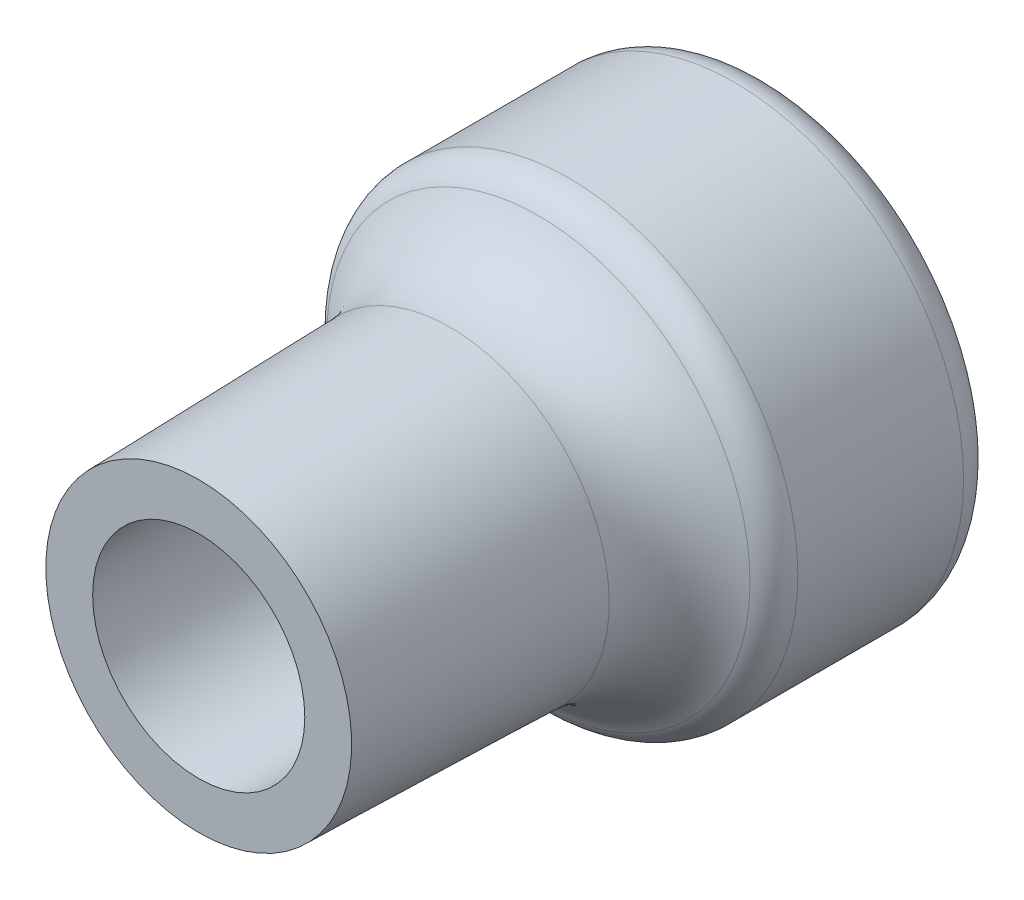
SolidWorks part; units mm, degrees
ref_plane "Front" through (0, 0, 0) normal (0, 0, 1) x (1, 0, 0)
ref_plane "Top" through (0, 0, 0) normal (0, 1, 0) x (1, 0, 0)
ref_plane "Right" through (0, 0, 0) normal (1, 0, 0) x (0, 0, -1)
ref_axis "Axis1" through (0, 0, 55) along (0, 0, -1)
sketch "Sketch1" plane through (0, 0, 0) normal (1, 0, 0) x (0, 0, -1)
  line L0 (-18.2441, 0) -> (18.2441, 0) construction
  line L1 (-18.2441, 11.1) -> (0, 11.557)
  line L4 (7.9377, 11.557) -> (7.9377, 7.5)
  line L5 (7.9377, 7.5) -> (-18.2441, 7.7)
  line L6 (-18.2441, 7.7) -> (-18.2441, 11.1)
  line L8 (6.9942, 16.637) -> (23.1777, 16.637)
  line L9 (23.1777, 16.637) -> (23.1777, 11.557)
  line L10 (7.9377, 11.557) -> (23.1777, 11.557)
  arc A1 (6.9942, 16.637) -> (0, 11.557) centre (-0.1908, 19.1746) cw
  point P4 (0, 0)
  dimension "D8" = 7.62
  dimension "D1" = 11.1
  dimension "D2" = 11.557
  dimension "D3" = 7.7
  dimension "D4" = 7.5
  dimension "D5" = 15.24
  dimension "D6" = 26.1819
  dimension "D7" = 5.08
  dimension "D9" = 18.2441
  dimension "D10" = 7.9377
  dimension "D11" = 16.1835
revolve "Revolve1" add sketch "Sketch1" angle 360 about L0
fillet "Fillet1" radius 5.08 1 edges at (0, -7.5, -7.9377)
fillet "Fillet2" radius 2.54 2 edges at (0, -16.637, -23.1777) (0, -16.637, -6.9942)
